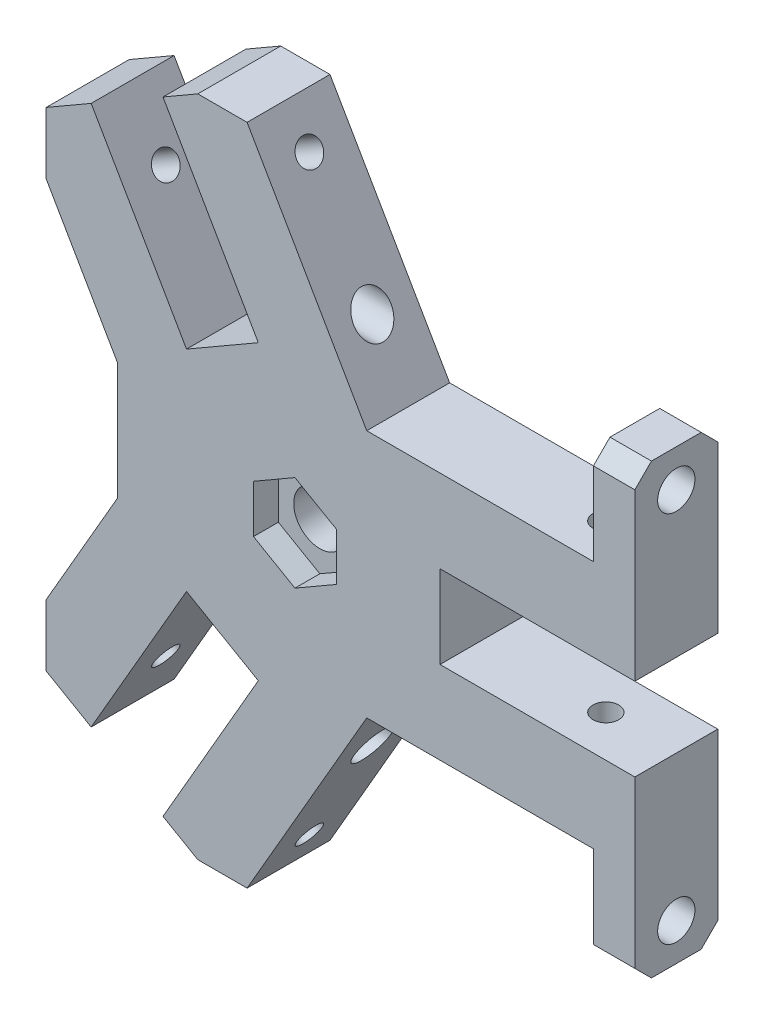
SolidWorks part; units mm, degrees
ref_plane "Front" through (0, 0, 0) normal (0, 0, 1) x (1, 0, 0)
ref_plane "Top" through (0, 0, 0) normal (0, 1, 0) x (1, 0, 0)
ref_plane "Right" through (0, 0, 0) normal (1, 0, 0) x (0, 0, -1)
sketch "Sketch1" plane through (0, 0, 0) normal (0, 0, 1) x (1, 0, 0)
  line L1 (0, 0) -> (71, 0)
  line L2 (0, 0) -> (0, 80)
  line L3 (0, 80) -> (71, 80)
  line L4 (71, 0) -> (71, 80)
  dimension "D1" = 80
  dimension "D2" = 71
extrude "Boss-Extrude1" add sketch "Sketch1" along normal blind 10
sketch "Sketch2" plane through (0, 0, 10) normal (0, 0, 1) x (1, 0, 0)
  line L1 (0, 80) -> (0, 0) construction
  line L2 (18.75, 59.4856) -> (18.75, 20.5144) construction
  line L3 (18.75, 20.5144) -> (52.5, 40) construction
  line L4 (52.5, 40) -> (18.75, 59.4856) construction
  circle A0 centre (30, 40) radius 22.5 construction
  point P3 (0, 40)
  dimension "D1" = 22.5
  dimension "D3" = 30
ref_axis "Axis1" through (30, 40, 10) along (0, 0, -1)
sketch "Sketch3" plane through (0, 0, 10) normal (0, 0, 1) x (1, 0, 0)
  line L0 (25.5801, 57.6554) -> (16.9199, 52.6554)
  line L1 (25.5801, 57.6554) -> (20.5801, 66.3157)
  line L2 (16.9199, 52.6554) -> (11.9199, 61.3157)
  line L3 (20.5801, 66.3157) -> (11.9199, 61.3157)
  line L4 (25.5801, 57.6554) -> (11.9199, 61.3157) construction
  line L5 (16.9199, 52.6554) -> (20.5801, 66.3157) construction
  line L6 (11.9199, 18.6843) -> (20.5801, 13.6843)
  line L7 (11.9199, 18.6843) -> (16.9199, 27.3446)
  line L8 (20.5801, 13.6843) -> (25.5801, 22.3446)
  line L9 (16.9199, 27.3446) -> (25.5801, 22.3446)
  line L10 (11.9199, 18.6843) -> (25.5801, 22.3446) construction
  line L11 (20.5801, 13.6843) -> (16.9199, 27.3446) construction
  line L13 (47.5, 45) -> (57.5, 45)
  line L14 (47.5, 45) -> (47.5, 35)
  line L15 (47.5, 35) -> (57.5, 35)
  line L16 (57.5, 45) -> (57.5, 35)
  line L17 (47.5, 45) -> (57.5, 35) construction
  line L18 (47.5, 35) -> (57.5, 45) construction
  point P0 (52.5, 40)
  point P1 (18.75, 59.4856)
  point P2 (18.75, 20.5144)
  dimension "D1" = 60
  dimension "D2" = 60
  dimension "D3" = 10
  dimension "D4" = 10
  dimension "D5" = 10
  dimension "D6" = 10
  dimension "D7" = 10
  dimension "D8" = 10
extrude "Cut-Extrude1" cut sketch "Sketch3" against normal blind 10
sketch "Sketch4" plane through (0, 45, 0) normal (0, -1, 0) x (1, 0, 0)
  line L0 (52.5, 7.2) -> (71, 7.2)
  line L1 (71, 10) -> (71, 0) construction
  line L2 (71, 7.2) -> (71, 2.8)
  line L3 (71, 2.8) -> (52.5, 2.8)
  line L4 (57.5, 10) -> (47.5, 10) construction
  arc A0 (52.5, 2.8) -> (52.5, 7.2) centre (52.5, 5) cw
  point P10 (52.5, 10)
  dimension "D1" = 2.2
  dimension "D2" = 5
sketch "Sketch5" plane through (0, 0, 10) normal (0, 0, 1) x (1, 0, 0)
  line L1 (57.5, 45) -> (85.6587, 45)
  line L2 (57.5, 45) -> (57.5, 35)
  line L3 (57.5, 35) -> (85.6587, 35)
  line L4 (85.6587, 45) -> (85.6587, 35)
extrude "Cut-Extrude3" cut sketch "Sketch5" against normal blind 10
sketch "Sketch6" plane through (9.5096, -5.4904, 0) normal (-0.866, 0.5, 0) x (0, 0, 1)
  line L0 (2.8, 27.141) -> (2.8, -15.6837)
  line L1 (2.8, -15.6837) -> (7.2, -15.6837)
  line L2 (7.2, -15.6837) -> (7.2, 27.141)
  line L3 (10, 22.141) -> (10, 32.141) construction
  arc A0 (2.8, 27.141) -> (7.2, 27.141) centre (5, 27.141) cw
  point P8 (10, 27.141)
  dimension "D1" = 2.2
  dimension "D2" = 5
  dimension "D3" = 4.4
pattern_circular "CirPattern1" count 3 over 360 about axis through (30, 40, 10) along (0, 0, -1) of "Cut-Extrude3"
ref_plane "Plane1" through (39.8205, 22.9904, 0) normal (0.866, 0.5, 0) x (0, 0, -1)
ref_plane "Plane2" through (5.1795, -2.9904, 0) normal (-0.866, 0.5, 0) x (0, 0, -1)
sketch "Sketch7" plane through (44.1506, 25.4904, 0) normal (-0.866, -0.5, 0) x (0, 0, 1)
  line L0 (2.8, 42.141) -> (2.8, 92.141)
  line L1 (2.8, 92.141) -> (7.2, 92.141)
  line L2 (7.2, 92.141) -> (7.2, 42.141)
  line L3 (10, 37.141) -> (10, 62.9423) construction
  arc A0 (2.8, 42.141) -> (7.2, 42.141) centre (5, 42.141) ccw
  dimension "D1" = 2.2
  dimension "D2" = 5
  dimension "D3" = 4.4
  dimension "D4" = 50
hole_wizard "M6 Clearance Hole1" positions "Sketch8" profile "Sketch9" hole size "M6" standard "ISO" end condition through all
sketch "Sketch8" plane through (0, 0, 10) normal (0, 0, 1) x (1, 0, 0)
  point P0 (30, 40)
sketch "Sketch9" plane through (30, 40, 10) normal (1, 0, 0) x (0, -1, 0)
  line L0 (0, 0) -> (0, 10)
  line L1 (0, 10) -> (3.15, 10)
  line L2 (3.15, 10) -> (3.15, 0)
  line L5 (3.15, 0) -> (0, 0)
  line L11 (0, -6.35) -> (0, 107.95) construction
  dimension "Thru Hole Dia." = 6.3
  dimension "Thru Hole Depth" = 10
sketch "Sketch10" plane through (0, 0, 10) normal (0, 0, 1) x (1, 0, 0)
  line L0 (16.9199, 52.6554) -> (25.5801, 57.6554) construction
  line L1 (30, 45.7735) -> (25, 42.8868)
  line L2 (25, 42.8868) -> (25, 37.1132)
  line L3 (25, 37.1132) -> (30, 34.2265)
  line L4 (30, 34.2265) -> (35, 37.1132)
  line L5 (35, 37.1132) -> (35, 42.8868)
  line L6 (35, 42.8868) -> (30, 45.7735)
  circle A0 centre (30, 40) radius 5 construction
  dimension "D1" = 10
extrude "Cut-Extrude6" cut sketch "Sketch10" against normal blind 3
sketch "Sketch11" plane through (0, 0, 0) normal (0, -1, 0) x (1, 0, 0)
  line L0 (12.6795, 10) -> (71, 10) construction
  circle A0 centre (62.5, 5) radius 1.55
  dimension "D1" = 3.1
  dimension "D2" = 5
  dimension "D3" = 10
extrude "Cut-Extrude7" cut sketch "Sketch11" against normal through all
pattern_circular "CirPattern2" count 3 over 360 about axis through (30, 40, 7) along (0, 0, -1) of "Cut-Extrude7"
sketch "Sketch12" plane through (0, 0, 10) normal (0, 0, 1) x (1, 0, 0)
  line L0 (71, 0) -> (71, 25)
  line L1 (71, 0) -> (71, 35) construction
  line L2 (71, 25) -> (38.6603, 25)
  line L3 (38.6603, 25) -> (24.2265, 0)
  line L4 (12.6795, 0) -> (71, 0) construction
  line L5 (24.2265, 0) -> (71, 0)
  line L6 (12.6795, 0) -> (25.5801, 22.3446) construction
  line L8 (47.5, 35) -> (71, 35) construction
  dimension "D1" = 10
  dimension "D2" = 10
extrude "Cut-Extrude8" cut sketch "Sketch12" against normal blind 10
ref_plane "Plane3" through (0, 40, 0) normal (0, -1, 0) x (-1, 0, 0)
mirror "Mirror1" about plane through (0, 40, 0) normal (0, -1, 0) of "Cut-Extrude8"
sketch "Sketch13" plane through (0, 0, 10) normal (0, 0, 1) x (1, 0, 0)
  line L0 (0, 61.9615) -> (8.6244, 47.0237)
  line L1 (0, 80) -> (0, 0) construction
  line L2 (8.6244, 47.0237) -> (8.6244, 32.9763)
  line L3 (8.6244, 32.9763) -> (0, 18.0385)
  line L4 (0, 18.0385) -> (0, 61.9615)
  line L5 (1.1325, 80) -> (16.9199, 52.6554) construction
  line L6 (16.9199, 27.3446) -> (1.1325, 0) construction
  circle A0 centre (30, 40) radius 22.5 construction
  dimension "D1" = 10
extrude "Cut-Extrude9" cut sketch "Sketch13" against normal blind 10
sketch "Sketch14" plane through (0, 0, 10) normal (0, 0, 1) x (1, 0, 0)
  line L0 (-3.2404, 12.426) -> (22.7404, -2.574)
  line L1 (22.7404, -2.574) -> (18.1699, -10.4904)
  line L2 (18.1699, -10.4904) -> (-7.8109, 4.5096)
  line L3 (-7.8109, 4.5096) -> (-3.2404, 12.426)
  line L4 (25.5801, 22.3446) -> (16.9199, 27.3446) construction
  line L5 (38.6603, 25) -> (24.2265, 0) construction
  line L6 (0, 18.0385) -> (8.6244, 32.9763) construction
  dimension "D1" = 23
extrude "Cut-Extrude10" cut sketch "Sketch14" against normal blind 10
mirror "Mirror2" about plane through (0, 40, 0) normal (0, -1, 0) of "Cut-Extrude10"
sketch "Sketch15" plane through (0, 0, 10) normal (0, 0, 1) x (1, 0, 0)
  line L0 (71, 45) -> (71, 55) construction
  line L1 (71, 19) -> (182, 19)
  line L2 (71, 19) -> (71, 61)
  line L3 (71, 61) -> (182, 61)
  line L4 (182, 19) -> (182, 61)
  line L5 (0, 0) -> (0, 81.4596) construction
  point P6 (71, 40)
  dimension "D1" = 42
  dimension "D2" = 182
extrude "Boss-Extrude2" add sketch "Sketch15" against normal blind 10
sketch "Sketch16" plane through (0, 0, 10) normal (0, 0, 1) x (1, 0, 0)
  line L1 (71, 50.5) -> (96, 50.5)
  line L2 (71, 50.5) -> (71, 29.5)
  line L3 (71, 29.5) -> (96, 29.5)
  line L4 (96, 50.5) -> (96, 29.5)
  line L5 (71, 45) -> (71, 35) construction
  line L7 (182, 61) -> (71, 61) construction
  dimension "D1" = 25
  dimension "D2" = 21
  dimension "D3" = 10.5
sketch "Sketch18" plane through (0, 0, 10) normal (0, 0, 1) x (1, 0, 0)
  line L0 (182, 61) -> (71, 61) construction
  line L1 (113.8, 24.5) -> (82.8, 24.5)
  line L2 (113.8, 24.5) -> (113.8, 55.5)
  line L3 (113.8, 55.5) -> (82.8, 55.5)
  line L4 (82.8, 24.5) -> (82.8, 55.5)
  line L5 (113.8, 24.5) -> (82.8, 55.5) construction
  line L6 (113.8, 55.5) -> (82.8, 24.5) construction
  line L7 (71, 61) -> (71, 55) construction
  point P0 (98.3, 40)
  dimension "D1" = 31
  dimension "D2" = 31
  dimension "D3" = 68.3
  dimension "D4" = 5.5
  dimension "D5" = 11.8
sketch "Sketch21" plane through (0, 0, 10) normal (0, 0, 1) x (1, 0, 0)
  line L4 (97.55, 40) -> (99.05, 40) construction
  line L5 (113.8, 24.5) -> (82.8, 55.5) construction
  line L6 (97.55, 47.5) -> (99.05, 47.5)
  line L7 (97.55, 32.5) -> (99.05, 32.5)
  arc A2 (97.55, 47.5) -> (97.55, 32.5) centre (97.55, 40) ccw
  arc A3 (99.05, 32.5) -> (99.05, 47.5) centre (99.05, 40) ccw
  point P5 (98.3, 40)
  dimension "D1" = 15
  dimension "D2" = 1.5
sketch "Sketch22" plane through (0, 0, 10) normal (0, 0, 1) x (1, 0, 0)
  line L0 (182, 19) -> (182, 61) construction
  line L1 (182, 67) -> (167, 67)
  line L2 (182, 67) -> (182, 13)
  line L3 (182, 13) -> (167, 13)
  line L4 (167, 67) -> (167, 13)
  point P6 (182, 40)
  dimension "D1" = 15
  dimension "D2" = 54
extrude "Boss-Extrude3" add sketch "Sketch22" against normal blind 10
sketch "Sketch23" plane through (182, 0, 0) normal (1, 0, 0) x (0, 0, -1)
  line L0 (-5, 62.5) -> (-5, 17.5) construction
  point P2 (-5, 40)
  dimension "D1" = 45
  dimension "D2" = 5
hole_wizard "M4 Clearance Hole1" positions "Sketch24" profile "Sketch25" hole size "M4" standard "DIN"
sketch "Sketch24" plane through (182, 0, 0) normal (1, 0, 0) x (0, 0, -1)
  point P0 (-5, 62.5)
  point P3 (-5, 17.5)
sketch "Sketch25" plane through (182, 62.5, 5) normal (0, 1, 0) x (0, 0, -1)
  line L0 (0, 0) -> (0, 31.3519)
  line L1 (0, 31.3519) -> (2.25, 30)
  line L2 (2.25, 30) -> (2.25, 0)
  line L5 (2.25, 0) -> (0, 0)
  line L10 (0, 31.3519) -> (-2.25, 30) construction
  line L11 (0, -6.35) -> (0, 107.95) construction
  dimension "Hole Dia." = 4.5
  dimension "Hole Depth" = 30
  dimension "Drill Angle" = 118
sketch "Sketch26" plane through (0, 0, 10) normal (0, 0, 1) x (1, 0, 0)
  line L0 (119.3, 61) -> (119.3, 55)
  line L1 (167, 61) -> (71, 61) construction
  line L2 (119.3, 55) -> (167, 55)
  line L3 (167, 55) -> (167, 61)
  line L4 (167, 61) -> (119.3, 61)
  dimension "D1" = 5.5
  dimension "D2" = 6
extrude "Cut-Extrude13" cut sketch "Sketch26" against normal blind 10
mirror "Mirror3" about plane through (0, 40, 0) normal (0, -1, 0) of "Cut-Extrude13"
chamfer "Chamfer1" distance 4 angle 60 2 edges at (119.3, 25, 5) (119.3, 55, 5) first distance on face at (143.15, 25, 5) first distance on face at (143.15, 55, 5)
sketch "Sketch27" plane through (0, 0, 10) normal (0, 0, 1) x (1, 0, 0)
  line L1 (71, 61) -> (77.3, 61)
  line L2 (71, 61) -> (71, 55)
  line L3 (71, 55) -> (77.3, 55)
  line L4 (77.3, 61) -> (77.3, 55)
  dimension "D1" = 6
  dimension "D2" = 5.5
extrude "Cut-Extrude14" cut sketch "Sketch27" against normal blind 10
mirror "Mirror4" about plane through (0, 40, 0) normal (0, -1, 0) of "Cut-Extrude14"
chamfer "Chamfer2" distance 4 angle 60 2 edges at (77.3, 55, 5) (77.3, 25, 5) first distance on face at (57.9801, 55, 5) first distance on face at (57.9801, 25, 5)
extrude "Cut-Extrude15" cut sketch "Sketch21" against normal blind 10
sketch "Sketch28" plane through (0, 0, 10) normal (0, 0, 1) x (1, 0, 0)
  line L0 (97.55, 40) -> (99.05, 40) construction
  line L1 (97.55, 51.25) -> (99.05, 51.25)
  line L2 (97.55, 28.75) -> (99.05, 28.75)
  circle A0 centre (98.3, 40) radius 11 construction
  arc A1 (97.55, 51.25) -> (97.55, 28.75) centre (97.55, 40) ccw
  arc A2 (99.05, 28.75) -> (99.05, 51.25) centre (99.05, 40) ccw
  point P5 (98.3, 40)
  dimension "D1" = 22
  dimension "D2" = 11.25
  dimension "D3" = 1.5
extrude "Cut-Extrude16" cut sketch "Sketch28" against normal blind 2.2
sketch "Sketch29" plane through (0, 0, 10) normal (0, 0, 1) x (1, 0, 0)
  line L0 (82.05, 55.5) -> (83.55, 55.5) construction
  line L1 (113.8, 55.5) -> (82.8, 55.5) construction
  line L2 (82.05, 57.2) -> (83.55, 57.2)
  line L3 (82.05, 53.8) -> (83.55, 53.8)
  line L4 (113.05, 53.8) -> (114.55, 53.8)
  line L5 (113.05, 57.2) -> (114.55, 57.2)
  line L6 (113.05, 55.5) -> (114.55, 55.5) construction
  line L7 (113.05, 22.8) -> (114.55, 22.8)
  line L8 (113.05, 26.2) -> (114.55, 26.2)
  line L9 (113.05, 24.5) -> (114.55, 24.5) construction
  line L10 (82.05, 22.8) -> (83.55, 22.8)
  line L11 (82.05, 26.2) -> (83.55, 26.2)
  line L12 (82.05, 24.5) -> (83.55, 24.5) construction
  arc A0 (82.05, 57.2) -> (82.05, 53.8) centre (82.05, 55.5) ccw
  arc A1 (83.55, 53.8) -> (83.55, 57.2) centre (83.55, 55.5) ccw
  arc A2 (113.05, 57.2) -> (113.05, 53.8) centre (113.05, 55.5) ccw
  arc A3 (114.55, 53.8) -> (114.55, 57.2) centre (114.55, 55.5) ccw
  arc A4 (113.05, 26.2) -> (113.05, 22.8) centre (113.05, 24.5) ccw
  arc A5 (114.55, 22.8) -> (114.55, 26.2) centre (114.55, 24.5) ccw
  arc A6 (82.05, 26.2) -> (82.05, 22.8) centre (82.05, 24.5) ccw
  arc A7 (83.55, 22.8) -> (83.55, 26.2) centre (83.55, 24.5) ccw
  point P5 (82.8, 55.5)
  point P15 (113.8, 55.5)
  point P22 (113.8, 24.5)
  point P29 (82.8, 24.5)
  dimension "D1" = 3.4
  dimension "D2" = 1.5
  dimension "D3" = 2
  dimension "D4" = 2
extrude "Cut-Extrude17" cut sketch "Sketch29" against normal blind 10
sketch "Sketch30" plane through (0, 0, 10) normal (0, 0, 1) x (1, 0, 0)
  line L0 (167, 67) -> (167, 55) construction
  line L1 (134, 29.5) -> (155, 29.5) construction
  line L2 (134, 29.5) -> (134, 50.5) construction
  line L3 (134, 50.5) -> (155, 50.5) construction
  line L4 (155, 29.5) -> (155, 50.5) construction
  line L6 (123.3, 55) -> (167, 55) construction
  dimension "D1" = 21
  dimension "D2" = 21
  dimension "D3" = 12
  dimension "D4" = 4.5
hole_wizard "M4 Clearance Hole2" positions "Sketch31" profile "Sketch32" hole size "M4" standard "DIN" end condition through all
sketch "Sketch31" plane through (0, 0, 10) normal (0, 0, 1) x (1, 0, 0)
  point P0 (134, 50.5)
  point P3 (155, 50.5)
  point P6 (155, 29.5)
  point P9 (134, 29.5)
sketch "Sketch32" plane through (134, 50.5, 10) normal (1, 0, 0) x (0, -1, 0)
  line L0 (0, 0) -> (0, 10)
  line L1 (0, 10) -> (2.25, 10)
  line L2 (2.25, 10) -> (2.25, 0)
  line L5 (2.25, 0) -> (0, 0)
  line L11 (0, -6.35) -> (0, 107.95) construction
  dimension "Thru Hole Dia." = 4.5
  dimension "Thru Hole Depth" = 10
sketch "Sketch33" plane through (71, 0, 0) normal (-1, 0, 0) x (0, 0, 1)
  line L1 (-10, 85) -> (20, 85)
  line L2 (-10, 85) -> (-10, -5)
  line L3 (-10, -5) -> (20, -5)
  line L4 (20, 85) -> (20, -5)
  dimension "D1" = 10
  dimension "D2" = 30
  dimension "D3" = 90
  dimension "D4" = 5
extrude "Cut-Extrude18" cut sketch "Sketch33" against normal through all contours L4 L3 L2 L1
sketch "Sketch34" plane through (71, 0, 0) normal (1, 0, 0) x (0, 0, -1)
  line L5 (0, 45) -> (0, 67)
  line L6 (0, 67) -> (-10, 67)
  line L7 (-10, 67) -> (-10, 45)
  line L8 (0, 45) -> (0, 35) construction
  line L9 (-10, 45) -> (0, 45)
  point P18 (0, 40)
  dimension "D1" = 27
  dimension "D2" = 22
  dimension "D3" = 10
  dimension "D4" = 10
extrude "Boss-Extrude4" add sketch "Sketch34" against normal blind 5
mirror "Mirror5" about plane through (0, 40, 0) normal (0, -1, 0) of "Boss-Extrude4"
sketch "Sketch35" plane through (71, 0, 0) normal (1, 0, 0) x (0, 0, -1)
  line L0 (-5, 62.5) -> (-5, 17.5)
  line L1 (-10, 67) -> (-10, 45) construction
  line L2 (0, 67) -> (-10, 67) construction
  dimension "D1" = 45
  dimension "D2" = 5
  dimension "D3" = 4.5
sketch "Sketch38" plane through (71, 0, 0) normal (1, 0, 0) x (0, 0, -1)
  circle A0 centre (-5, 62.5) radius 2.25
  circle A1 centre (-5, 17.5) radius 2.25
  dimension "D1" = 4.5
  dimension "D2" = 4.5
extrude "Cut-Extrude20" cut sketch "Sketch38" against normal blind 41
chamfer "Chamfer3" distance 2 angle 45 4 edges at (68.5, 67, 0) (68.5, 67, 10) (68.5, 13, 0) (68.5, 13, 10)
